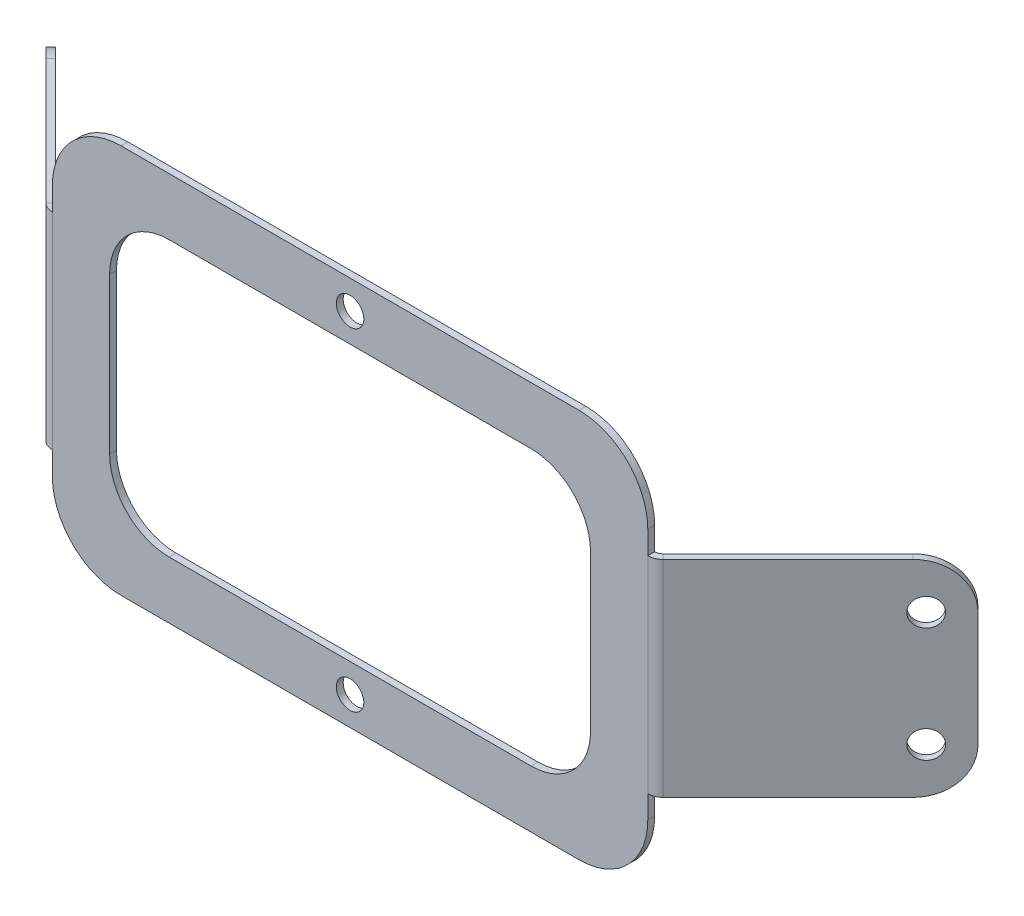
SolidWorks part; units mm, degrees
note: The reader was unsure of these and kept them because the rebuilt part matched: flange length of "Ребро-кромка1".
ref_plane "Спереди" through (0, 0, 0) normal (0, 0, 1) x (1, 0, 0)
ref_plane "Сверху" through (0, 0, 0) normal (0, 1, 0) x (1, 0, 0)
ref_plane "Справа" through (0, 0, 0) normal (1, 0, 0) x (0, 0, -1)
sketch "Sketch1" plane through (0, 0, 0) normal (0, 0, 1) x (1, 0, 0)
  line L1 (15, 0) -> (115, 0)
  line L2 (0, 15) -> (0, 70)
  line L3 (15, 85) -> (115, 85)
  line L4 (130, 15) -> (130, 70)
  line L9 (104.5, 12.5) -> (25.5, 12.5)
  line L10 (117.5, 25.5) -> (117.5, 59.5)
  line L11 (104.5, 72.5) -> (25.5, 72.5)
  line L12 (12.5, 25.5) -> (12.5, 59.5)
  arc A4 (25.5, 72.5) -> (12.5, 59.5) centre (25.5, 59.5) ccw
  arc A5 (25.5, 12.5) -> (12.5, 25.5) centre (25.5, 25.5) cw
  arc A6 (117.5, 59.5) -> (104.5, 72.5) centre (104.5, 59.5) ccw
  arc A7 (104.5, 12.5) -> (117.5, 25.5) centre (104.5, 25.5) ccw
  arc A8 (0, 70) -> (15, 85) centre (15, 70) cw
  arc A9 (15, 0) -> (0, 15) centre (15, 15) cw
  arc A10 (115, 85) -> (130, 70) centre (115, 70) cw
  arc A11 (115, 0) -> (130, 15) centre (115, 15) ccw
  point P13 (12.5, 12.5)
  point P16 (117.5, 72.5)
  point P19 (117.5, 12.5)
  point P22 (0, 85)
  point P25 (0, 0)
  point P30 (130, 0)
  dimension "D4" = 105
  dimension "D7" = 13
  dimension "D8" = 15
  dimension "D1" = 130
  dimension "D2" = 85
  dimension "D5" = 12.5
  dimension "D3" = 60
  dimension "D6" = 12.5
base flange "Base-Flange1" sketch "Sketch1" thickness 1.5 reverse thickness direction no parameters "D1"=1.85
edge flange "Ребро-кромка1" sketch "Sketch10" flange profiles "Sketch10", "Sketch11" flange angle 135 flange length 50 flange position bend outside bend radius 1.85 thickness 1.5 parameters "D6"=10, "D8"=1
sketch "Sketch10" plane through (0, 0, -1.5) normal (0.7071, 0, -0.7071) x (0, -1, 0)
  line L3 (-65, 49.3787) -> (-20, 49.3787)
  line L5 (-15, 0) -> (-70, 0) construction
  line L6 (-20, 0) -> (-65, 0)
  line L7 (-65, 0) -> (-65, 49.3787)
  line L8 (-20, 0) -> (-20, 49.3787)
sketch "Sketch11" plane through (130, 0, -1.5) normal (-0.7071, 0, -0.7071) x (0, 1, 0)
  line L0 (70, 0) -> (15, 0) construction
  line L1 (65, 0) -> (20, 0)
  line L3 (65, 49.3787) -> (20, 49.3787)
  line L5 (20, 0) -> (20, 49.3787)
  line L7 (65, 0) -> (65, 49.3787)
bend "EdgeBend1" bend radius 1.85 bend angle 45 parameters "D5"=1
bend "EdgeBend2" bend radius 1.85 bend angle 45 parameters "D5"=2
sketch "Sketch12" plane through (65.6938, 0, 65.6938) normal (0.7071, 0, 0.7071) x (0.7071, 0, -0.7071)
  line L0 (142.9051, 65) -> (142.9051, 20) construction
  line L1 (142.9051, 20) -> (94.2927, 20) construction
  line L2 (94.2927, 65) -> (142.9051, 65) construction
  circle A0 centre (134.9051, 30) radius 3
  circle A1 centre (134.9051, 55) radius 3
  dimension "D1" = 6
  dimension "D2" = 8
  dimension "D3" = 10
  dimension "D5" = 10
  dimension "D4" = 2
extrude "Cut-Extrude1" cut sketch "Sketch12" against normal blind 10
fillet "Fillet1" radius 10 4 edges at (166.2126, 20, -35.8857) (166.2126, 65, -35.8857) (-36.2126, 20, -35.8857) (-36.2126, 65, -35.8857)
sketch "Sketch13" plane through (-0.6938, 0, 0.6938) normal (-0.7071, 0, 0.7071) x (0.7071, 0, 0.7071)
  line L0 (-2.3688, 20) -> (-40.9812, 20) construction
  line L1 (-50.9812, 30) -> (-50.9812, 55) construction
  line L2 (-40.9812, 65) -> (-2.3688, 65) construction
  circle A0 centre (-42.9812, 30) radius 3
  circle A1 centre (-42.9812, 55) radius 3
  dimension "D1" = 6
  dimension "D2" = 10
  dimension "D3" = 8
  dimension "D5" = 10
  dimension "D4" = 2
extrude "Cut-Extrude2" cut sketch "Sketch13" against normal blind 10
sketch "Sketch14" plane through (0, 0, -1.5) normal (0, 0, -1) x (-1, 0, 0)
  line L0 (-117.5, 25.5) -> (-117.5, 59.5) construction
  line L2 (-15, 0) -> (-115, 0) construction
  line L4 (-12.5, 42.5) -> (-117.5, 42.5) construction
  line L5 (-12.5, 59.5) -> (-12.5, 25.5) construction
  circle A0 centre (-65, 6.25) radius 3
  circle A1 centre (-65, 78.75) radius 3
  dimension "D1" = 6
  dimension "D2" = 52.5
  dimension "D3" = 6.25
extrude "Cut-Extrude3" cut sketch "Sketch14" against normal blind 10
sketch "Сгиб-Линии1" plane through (0, 0, 0) normal (0, 1, 0) x (1, 0, 0)
sketch "Граничная рамка1" plane through (0, 0, 0) normal (0, 1, 0) x (1, 0, 0)
sheet metal parameters "Листовой металл3" thickness 1.5 parameters "D1"=1.85
flat pattern "Развертка3" [suppressed]
sketch "Сгиб-Линии2" plane through (0, 0, 0) normal (0, 1, 0) x (1, 0, 0)
sketch "Граничная рамка2" [suppressed] plane through (0, 0, 0) normal (0, 1, 0) x (1, 0, 0)
sheet metal parameters "Листовой металл4" thickness 1.5 parameters "D1"=1.85
flat pattern "Развертка3" [suppressed]
sketch "Сгиб-Линии2" plane through (0, 0, 0) normal (0, 1, 0) x (1, 0, 0)
sketch "Граничная рамка2" [suppressed] plane through (0, 0, 0) normal (0, 1, 0) x (1, 0, 0)
bend of the flat pattern "Плоское состояние-<EdgeBend1>1"
bend of the flat pattern "Плоское состояние-<EdgeBend2>1"
sheet metal parameters "Листовой металл5" thickness 1.5 parameters "D1"=1.85
flat pattern "Развертка3" [suppressed]
sketch "Сгиб-Линии2" plane through (0, 0, 0) normal (0, 1, 0) x (1, 0, 0)
sketch "Граничная рамка2" [suppressed] plane through (0, 0, 0) normal (0, 1, 0) x (1, 0, 0)
bend of the flat pattern "Плоское состояние-<EdgeBend1>1"
bend of the flat pattern "Плоское состояние-<EdgeBend2>1"
sheet metal parameters "Листовой металл6" thickness 1.5 parameters "D1"=1.85
flat pattern "Развертка3" [suppressed]
sketch "Сгиб-Линии2" plane through (0, 0, 0) normal (0, 1, 0) x (1, 0, 0)
sketch "Граничная рамка2" [suppressed] plane through (0, 0, 0) normal (0, 1, 0) x (1, 0, 0)
bend of the flat pattern "Плоское состояние-<EdgeBend1>1"
bend of the flat pattern "Плоское состояние-<EdgeBend2>1"
sheet metal parameters "Листовой металл7" thickness 1.5 parameters "D1"=1.85
flat pattern "Развертка3" [suppressed]
sketch "Сгиб-Линии2" plane through (0, 0, 0) normal (0, 1, 0) x (1, 0, 0)
sketch "Граничная рамка2" [suppressed] plane through (0, 0, 0) normal (0, 1, 0) x (1, 0, 0)
bend of the flat pattern "Плоское состояние-<EdgeBend1>1"
bend of the flat pattern "Плоское состояние-<EdgeBend2>1"
